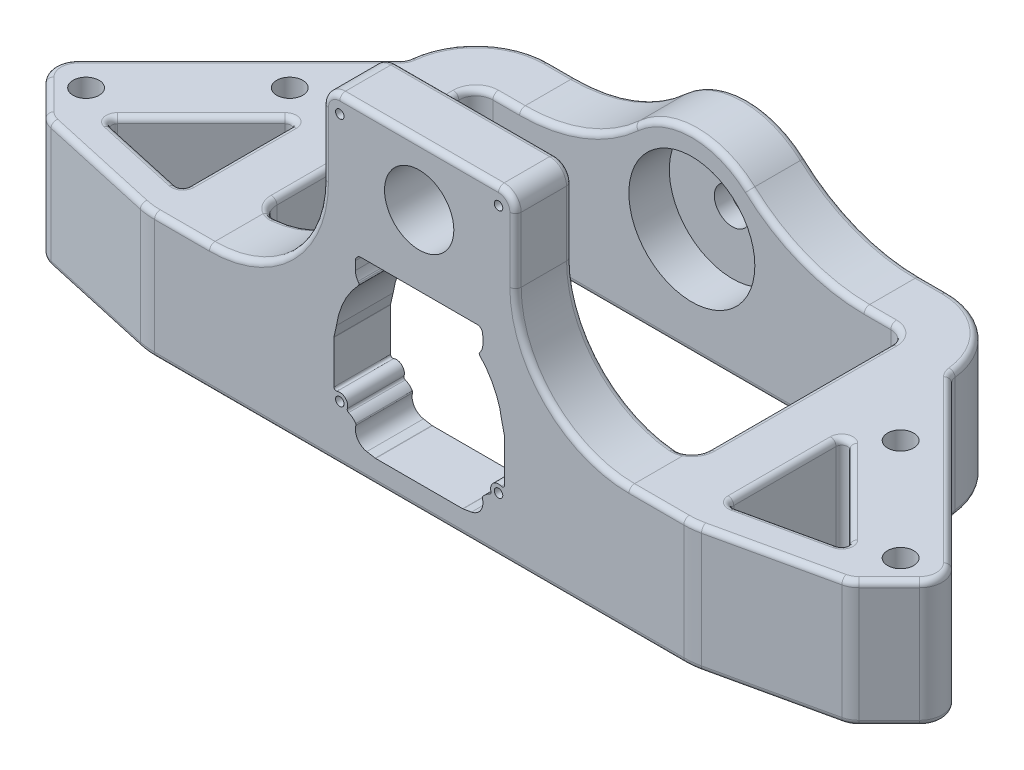
SolidWorks part; units mm, degrees
ref_plane "Front Plane" through (0, 0, 0) normal (0, 0, 1) x (1, 0, 0)
ref_plane "Top Plane" through (0, 0, 0) normal (0, 1, 0) x (1, 0, 0)
ref_plane "Right Plane" through (0, 0, 0) normal (1, 0, 0) x (0, 0, -1)
sketch "Sketch1" plane through (0, 0, 0) normal (0, 1, 0) x (1, 0, 0)
  line L0 (-48.1, -29.05) -> (-48.1, 29.05)
  line L1 (38.1, -19.05) -> (-38.1, -19.05)
  line L2 (38.1, -19.05) -> (38.1, 19.05)
  line L3 (38.1, 19.05) -> (-38.1, 19.05)
  line L4 (-38.1, -19.05) -> (-38.1, 19.05)
  line L5 (38.1, -19.05) -> (-38.1, 19.05) construction
  line L6 (38.1, 19.05) -> (-38.1, -19.05) construction
  line L11 (48.1, 29.05) -> (-48.1, 29.05)
  line L12 (48.1, -29.05) -> (48.1, 29.05)
  line L13 (48.1, -29.05) -> (-48.1, -29.05)
  line L14 (-79.8677, -15.0075) -> (-70.8875, -23.9877)
  line L15 (-70.8875, -23.9877) -> (-48.1, -1.2003)
  line L16 (-79.8677, -15.0075) -> (-48.1, 16.7603)
  line L17 (0, 0) -> (0, 65.6417) construction
  line L18 (-75.3776, -19.4976) -> (0, 55.88) construction
  line L19 (-48.1, -29.05) -> (-70.8875, -23.9877)
  line L20 (-48.1, -22.9037) -> (-65.8584, -18.9587)
  line L21 (48.1, -29.05) -> (70.8875, -23.9877)
  line L22 (48.1, -22.9037) -> (65.8584, -18.9587)
  line L23 (79.8677, -15.0075) -> (48.1, 16.7603)
  line L24 (79.8677, -15.0075) -> (70.8875, -23.9877)
  line L25 (70.8875, -23.9877) -> (48.1, -1.2003)
  line L26 (-75.3776, -19.4976) -> (-269.4077, -213.5277) construction
  circle A0 centre (-71.842, -15.962) radius 2.3
  circle A1 centre (-53.8815, 1.9985) radius 2.3
  circle A4 centre (53.8815, 1.9985) radius 2.3
  circle A5 centre (71.842, -15.962) radius 2.3
  point P0 (0, 0)
  point P21 (-75.3776, -19.4976)
  point P32 (-197.5656, -141.6856)
  point P34 (-215.5261, -159.6461)
  point P38 (-76.3322, -20.4522)
  point P40 (-101.6555, -5.7951)
  dimension "D10" = 4.6
  dimension "D1" = 10
  dimension "D2" = 45
  dimension "D3" = 55.88
  dimension "D4" = 5
  dimension "D5" = 76.2
  dimension "D6" = 12.7
  dimension "D7" = 25.4
  dimension "D8" = 76.2
  dimension "D9" = 38.1
  dimension "D11" = 6
  dimension "D12" = 381
  dimension "D13" = 101.6
  dimension "D14" = 177.8
  dimension "D15" = 25.4
  dimension "D16" = 228.6
extrude "Boss-Extrude1" add sketch "Sketch1" along normal blind 22.25 contours L13 L12 L11 L0 L1 L4 L3 L2 | L0 L20 L15 L19 | L21 L25 L22 L12 | L25 L24 L23 L12 A4 A5 | L16 L14 L15 L0 A1 A0 region at (-58.2884, 0, 23.8405) region at (-46.9762, 0, 25.9769) region at (58.2884, 0, 23.8405) region at (-61.7892, 0, 5.3806) region at (61.7892, 0, 5.3806)
extrude "Boss-Extrude2" add sketch "Sketch1<3>" along normal blind 15.85 from surface contours L13 L12 L11 L0 L1 L4 L3 L2 region at (-46.9762, 0, 25.9769) starting at face at (54.0195, 22.25, 14.3542)
sketch "Sketch1<3>" plane through (0, 0, 0) normal (0, 1, 0) x (1, 0, 0) same geometry as "Sketch1"
sketch "Sketch3" plane through (0, 0, 29.05) normal (0, 0, 1) x (1, 0, 0)
  line L0 (0, 0) -> (0, 38.1) construction
  line L1 (-48.1, 38.1) -> (48.1, 38.1) construction
  line L2 (7.7467, 4.2612) -> (9.2383, 4.5242)
  line L3 (-7.6773, 4.2551) -> (7.6773, 4.2551)
  line L4 (-9.2383, 4.5242) -> (-7.7467, 4.2612)
  line L5 (-15.0449, 19.0418) -> (-15.0449, 11.4779)
  line L6 (-14.5827, 21.1094) -> (-15.0348, 19.1309)
  line L7 (-10.7806, 29.7585) -> (-10.65, 29.5787)
  line L8 (-6.6626, 32.35) -> (-6.853, 32.6121)
  line L9 (6.853, 32.6121) -> (6.6626, 32.35)
  line L10 (10.65, 29.5787) -> (10.7806, 29.7585)
  line L11 (15.0348, 19.1309) -> (14.5827, 21.1094)
  line L12 (15.0449, 11.4779) -> (15.0449, 19.0418)
  line L13 (-48.1, 22.25) -> (-17, 22.25)
  line L14 (-17, 22.25) -> (-17, 56.7)
  line L15 (-17, 56.7) -> (17, 56.7)
  line L16 (17, 56.7) -> (17, 22.25)
  line L17 (17, 22.25) -> (48.1, 22.25)
  line L18 (48.1, 38.1) -> (48.1, 22.25) construction
  line L19 (48.1, 22.25) -> (48.1, 38.1)
  line L20 (48.1, 38.1) -> (17, 38.1)
  line L21 (-17, 38.1) -> (-48.1, 38.1)
  line L22 (-48.1, 38.1) -> (-48.1, 22.25)
  line L23 (-17, 38.1) -> (17, 38.1)
  line L24 (-11.2442, 31.1853) -> (-11.2442, 33.6774)
  line L25 (-11.2442, 33.6774) -> (11.1927, 33.6774)
  line L26 (11.1927, 33.6774) -> (11.2442, 31.1853)
  line L27 (-48.1, 22.25) -> (-70.8875, 22.25) construction
  circle A0 centre (14, 9.8) radius 0.75
  circle A1 centre (-14, 9.8) radius 0.75
  circle A2 centre (-14, 53.7) radius 0.75
  circle A3 centre (14, 53.7) radius 0.75
  circle A4 centre (0, 46.05) radius 6.114
  arc A5 (12.4458, 8.8644) -> (11.1887, 7.8314) centre (13.5, 6.3) ccw
  arc A6 (9.2383, 4.5242) -> (11.1504, 7.5831) centre (8.8168, 6.9147) ccw
  arc A7 (7.6773, 4.2551) -> (7.7467, 4.2612) centre (7.6773, 4.6551) ccw
  arc A8 (-7.7467, 4.2612) -> (-7.6773, 4.2551) centre (-7.6773, 4.6551) ccw
  arc A9 (-11.1504, 7.5831) -> (-9.2383, 4.5242) centre (-8.8168, 6.9147) ccw
  arc A10 (-11.1887, 7.8314) -> (-12.4458, 8.8644) centre (-13.5, 6.3) ccw
  arc A11 (-12.6734, 9.3602) -> (-14.5014, 11.1045) centre (-14, 9.8) ccw
  arc A12 (-15.0348, 19.1309) -> (-15.0449, 19.0418) centre (-14.6449, 19.0418) ccw
  arc A13 (-10.6753, 29.1957) -> (-14.5827, 21.1094) centre (0, 19.05) ccw
  arc A14 (-6.853, 32.6121) -> (-10.7806, 29.7585) centre (-8.8168, 31.1853) ccw
  arc A15 (6.2909, 32.2555) -> (-6.2909, 32.2555) centre (0, 19.05) ccw
  arc A16 (10.7806, 29.7585) -> (6.853, 32.6121) centre (8.8168, 31.1853) ccw
  arc A17 (14.5827, 21.1094) -> (10.6753, 29.1957) centre (0, 19.05) ccw
  arc A18 (15.0449, 19.0418) -> (15.0348, 19.1309) centre (14.6449, 19.0418) ccw
  arc A19 (14.5014, 11.1045) -> (12.6734, 9.3602) centre (14, 9.8) ccw
  spline S0 degree 3 poles (12.4458, 8.8644) (12.5392, 8.9027) (12.6157, 8.9767) (12.699, 9.1584) (12.7052, 9.2644) (12.6734, 9.3602) knots 0 0 0 0 0.000302 0.000302 0.000604 0.000604 0.000604 0.000604 weights 1 1 1 1 1 1
  spline S1 degree 3 poles (11.1504, 7.5831) (11.1264, 7.6668) (11.1406, 7.7587) (11.1887, 7.8314) knots 0 0 0 0 0.000258 0.000258 0.000258 0.000258 weights 1 1 1 1
  spline S2 degree 3 poles (-11.1887, 7.8314) (-11.1406, 7.7587) (-11.1264, 7.6668) (-11.1504, 7.5831) knots 0 0 0 0 0.000258 0.000258 0.000258 0.000258 weights 1 1 1 1
  spline S3 degree 3 poles (-12.6734, 9.3602) (-12.7052, 9.2644) (-12.699, 9.1582) (-12.6155, 8.9765) (-12.5392, 8.9027) (-12.4458, 8.8644) knots 0 0 0 0 0.000302 0.000302 0.000604 0.000604 0.000604 0.000604 weights 1 1 1 1 1 1
  spline S4 degree 3 poles (-15.0449, 11.4779) (-15.0449, 11.3476) (-14.9779, 11.2213) (-14.7643, 11.0748) (-14.6231, 11.0578) (-14.5014, 11.1045) knots 0 0 0 0 0.000388 0.000388 0.000776 0.000776 0.000776 0.000776 weights 1 1 1 1 1 1
  spline S5 degree 3 poles (-10.65, 29.5787) (-10.6088, 29.522) (-10.5888, 29.4526) (-10.5979, 29.3131) (-10.627, 29.2466) (-10.6753, 29.1957) knots 0 0 0 0 0.000207 0.000207 0.000415 0.000415 0.000415 0.000415 weights 1 1 1 1 1 1
  spline S6 degree 3 poles (-6.2909, 32.2555) (-6.3541, 32.2254) (-6.4259, 32.2184) (-6.5613, 32.2528) (-6.6214, 32.2934) (-6.6626, 32.35) knots 0 0 0 0 0.000207 0.000207 0.000414 0.000414 0.000414 0.000414 weights 1 1 1 1 1 1
  spline S7 degree 3 poles (6.6626, 32.35) (6.6214, 32.2934) (6.5617, 32.2529) (6.4263, 32.2184) (6.3541, 32.2254) (6.2909, 32.2555) knots 0 0 0 0 0.000207 0.000207 0.000414 0.000414 0.000414 0.000414 weights 1 1 1 1 1 1
  spline S8 degree 3 poles (10.6753, 29.1957) (10.627, 29.2466) (10.598, 29.3127) (10.5887, 29.4522) (10.6088, 29.522) (10.65, 29.5787) knots 0 0 0 0 0.000207 0.000207 0.000415 0.000415 0.000415 0.000415 weights 1 1 1 1 1 1
  spline S9 degree 3 poles (14.5014, 11.1045) (14.6231, 11.0578) (14.765, 11.075) (14.9783, 11.2218) (15.0449, 11.3476) (15.0449, 11.4779) knots 0 0 0 0 0.000388 0.000388 0.000776 0.000776 0.000776 0.000776 weights 1 1 1 1 1 1
  point P5 (0, 19.05)
  point P17 (0, 19.05)
  point P86 (0, 33.6774)
  point P90 (-48.1, 22.25)
  line M46 (48.1, 22.25) -> (48.1, 38.1)
  line M47 (48.1, 38.1) -> (-48.1, 38.1)
  line M48 (-48.1, 38.1) -> (-48.1, 22.25)
  dimension "D1" = 1.5
  dimension "D2" = 3
  dimension "D3" = 3
  dimension "D4" = 3
extrude "Boss-Extrude3" add sketch "Sketch3" against normal up to surface (10 mm away) contours L16 L15 L14 L23 A4 A3 A2 M47 region at (-16.6124, 47.4, 29.05) up to face at (0, 19.05, 19.05)
extrude "Cut-Extrude1" cut sketch "Sketch3<3>" against normal up to next contours L13 L14 M47 M48 | L16 L17 M46 M47 region at (-32.55, 30.175, 29.05) region at (32.55, 30.175, 29.05)
sketch "Sketch3<3>" plane through (0, 0, 29.05) normal (0, 0, 1) x (1, 0, 0) same geometry as "Sketch3"
extrude "Cut-Extrude2" cut sketch "Sketch3<4>" against normal up to next contours L3 L0 A15 S6 L8 A14 L7 S5 A13 L6 A12 L5 S4 A11 S3 A10 S2 A9 L4 A8 | L0 L3 A7 L2 A6 S1 A5 S0 A19 S9 L12 A18 L11 A17 S8 L10 A16 L9 S7 A15 | A1 | A0 | S6 A15 L25 L24 A14 L8 | S7 L9 A16 L26 L25 A15 region at (-6.6584, 18.6234, 29.05) region at (6.6584, 18.6234, 29.05) region at (-6.742, 33.2078, 29.05) region at (6.692, 33.2118, 29.05) region at (14, 9.8, 29.05) region at (-14, 9.8, 29.05)
sketch "Sketch3<4>" plane through (0, 0, 29.05) normal (0, 0, 1) x (1, 0, 0) same geometry as "Sketch3"
sketch "Sketch4" plane through (0, 0, -29.05) normal (0, 0, -1) x (-1, 0, 0)
  line L0 (0, 0) -> (0, 38.1) construction
  line L1 (17, 38.1) -> (-17, 38.1) construction
  line L5 (-17, 22.25) -> (-14.6547, 22.25)
  line L6 (-17, 22.25) -> (-17, 38.1)
  line L7 (-17, 38.1) -> (17, 38.1)
  line L8 (17, 38.1) -> (17, 22.25)
  line L9 (17, 22.25) -> (14.6547, 22.25)
  circle A0 centre (0, 19.05) radius 3.175
  circle A1 centre (0, 19.05) radius 15
  line M7 (17, 22.25) -> (17, 38.1)
  line M8 (17, 38.1) -> (-17, 38.1)
  line M9 (-17, 38.1) -> (-17, 22.25)
  dimension "D1" = 30
  dimension "D2" = 6.35
extrude "Cut-Extrude3" cut sketch "Sketch4" against normal up to next contours A1 L0 L7 L5 M9 | L0 A1 L9 M7 M8 | L0 A0 | A0 L0 region at (1.3475, 19.05, -29.05) region at (-1.3475, 19.05, -29.05) region at (10.8276, 32.9317, -29.05) region at (-10.8276, 32.9317, -29.05)
fillet "Fillet1" radius 20 2 edges at (17, 22.25, 24.05) (-17, 22.25, 24.05)
fillet "Fillet2" radius 3 2 edges at (-17, 56.7, 24.05) (17, 56.7, 24.05)
fillet "Fillet3" radius 1 2 edges at (11.1927, 33.6774, 24.05) (-11.2442, 33.6774, 24.05)
fillet "Fillet4" radius 1 6 edges at (65.8584, 11.125, 18.9587) (48.1, 11.125, 22.9037) (48.1, 11.125, 1.2003) (-48.1, 11.125, 1.2003) (-48.1, 11.125, 22.9037) (-65.8584, 11.125, 18.9587)
fillet "Fillet5" radius 3 4 edges at (-38.1, 11.125, -19.05) (38.1, 11.125, -19.05) (38.1, 11.125, 19.05) (-38.1, 11.125, 19.05)
fillet "Fillet6" radius 13 4 edges at (48.1, 11.125, -29.05) (-48.1, 11.125, -29.05) (-48.1, 11.125, 29.05) (48.1, 11.125, 29.05)
fillet "Fillet7" radius 4 4 edges at (79.8677, 11.125, 15.0075) (70.8875, 11.125, 23.9877) (-70.8875, 11.125, 23.9877) (-79.8677, 11.125, 15.0075)
sketch "Sketch5" plane through (0, 0, -19.05) normal (0, 0, 1) x (1, 0, 0)
  circle A0 centre (0, 19.05) radius 11.1125
  dimension "D1" = 22.225
extrude "Cut-Extrude4" cut sketch "Sketch5" against normal blind 7.1374
fillet "Fillet8" radius 30 2 edges at (14.6547, 22.25, -24.05) (-14.6547, 22.25, -24.05)
fillet "Fillet10" radius 2 2 edges at (-48.1, 11.125, -16.7603) (48.1, 11.125, -16.7603)
fillet "Fillet9" radius 1 9 edges at (57.1886, 22.25, 10.2889) (48.1, 0, 12.6358) (-48.1, 22.25, 12.6358) (-48.1, 0, 12.6358) (-38.1, 0, 0) (-22.2014, 28.7964, 19.05) (0, 0, -29.05) (-74.3752, 0, 20.4999) (-74.3752, 22.25, 20.4999)
